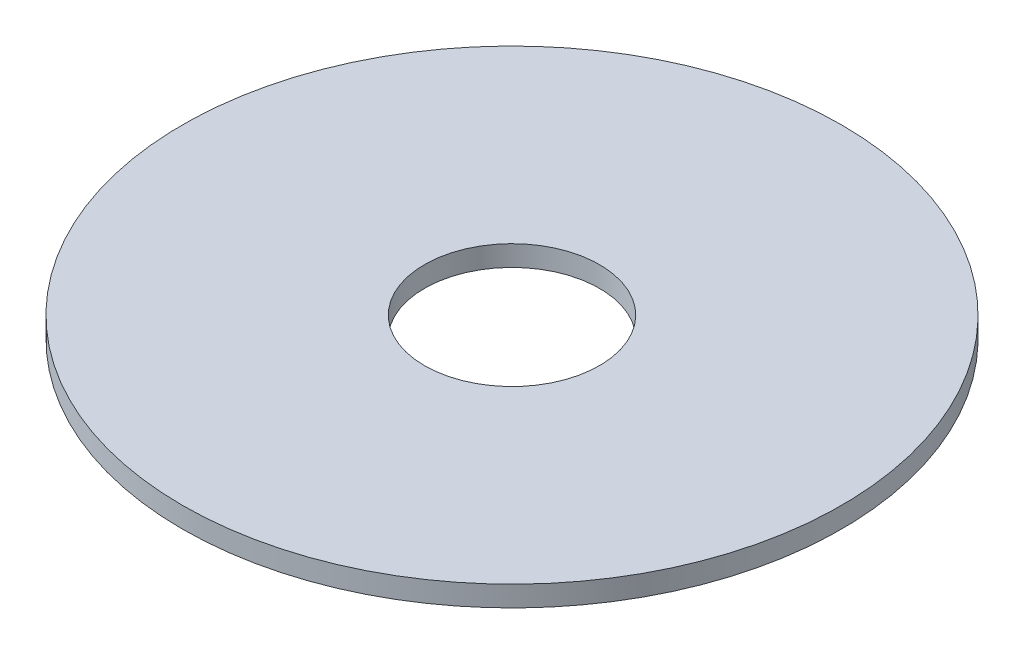
SolidWorks part; units mm, degrees
material "Delrin 2700 NC010, Low Viscosity Acetal Copolymer (SS)"
ref_plane "Front Plane" through (0, 0, 0) normal (0, 0, 1) x (1, 0, 0)
ref_plane "Top Plane" through (0, 0, 0) normal (0, 1, 0) x (1, 0, 0)
ref_plane "Right Plane" through (0, 0, 0) normal (1, 0, 0) x (0, 0, -1)
sketch "Sketch1" plane through (0, 0, 0) normal (0, 1, 0) x (1, 0, 0)
  circle A0 centre (0, 0) radius 25.4
  dimension "D1" = 50.8
extrude "Boss-Extrude1" add sketch "Sketch1" along normal blind 1.5875
sketch "Sketch2" plane through (0, 1.5875, 0) normal (0, 1, 0) x (1, 0, 0)
  circle A0 centre (0, 0) radius 3.175
  dimension "D1" = 6.35
hole_wizard "1/2 Clearance Hole1" positions "3DSketch1" profile "Sketch3" hole size "1/2" standard "ANSI Inch" end condition through all
sketch3d "3DSketch1"
  point P0 (0, 0, 0)
  point P4 (0, 1.5875, 0)
sketch "Sketch3" plane through (0, 1.5875, 0) normal (1, 0, 0) x (0, 0, 1)
  line L0 (0, 0) -> (0, 1.5875)
  line L1 (0, 1.5875) -> (6.7462, 1.5875)
  line L2 (6.7462, 1.5875) -> (6.7462, 0)
  line L5 (6.7462, 0) -> (0, 0)
  line L11 (0, -6.35) -> (0, 107.95) construction
  dimension "Thru Hole Dia." = 13.4925
  dimension "Thru Hole Depth" = 1.5875
